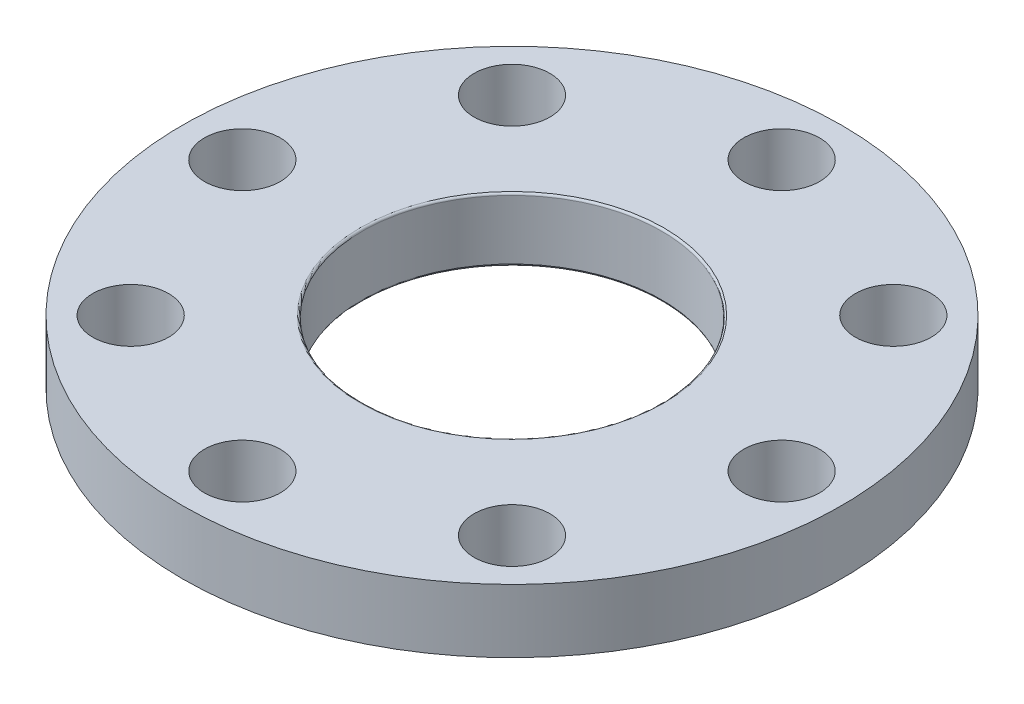
SolidWorks part; units mm, degrees
ref_plane "Front Plane" through (0, 0, 0) normal (0, 0, 1) x (1, 0, 0)
ref_plane "Top Plane" through (0, 0, 0) normal (0, 1, 0) x (1, 0, 0)
ref_plane "Right Plane" through (0, 0, 0) normal (1, 0, 0) x (0, 0, -1)
sketch "Sketch1" plane through (0, 0, 0) normal (0, 1, 0) x (1, 0, 0)
  circle A0 centre (0, 0) radius 16.5
  circle A1 centre (0, 0) radius 7.5
  dimension "D1" = 15
  dimension "D2" = 33
extrude "Boss-Extrude1" add sketch "Sketch1" along normal blind 3.175
fillet "Fillet1" radius 0.1 2 edges at (0, 0, 7.5) (0, 3.175, 7.5)
sketch "Sketch2" plane through (0, 3.175, 0) normal (0, 1, 0) x (-1, 0, 0)
  circle A0 centre (0, -13.5) radius 1.8986
  dimension "D2" = 3.7973
  dimension "D1" = 13.5
extrude "Cut-Extrude1" cut sketch "Sketch2" against normal through all
pattern_circular "CirPattern1" count 8 over 360 about axis through (0, 3.175, 0) along (0, -1, 0) of "Cut-Extrude1"
